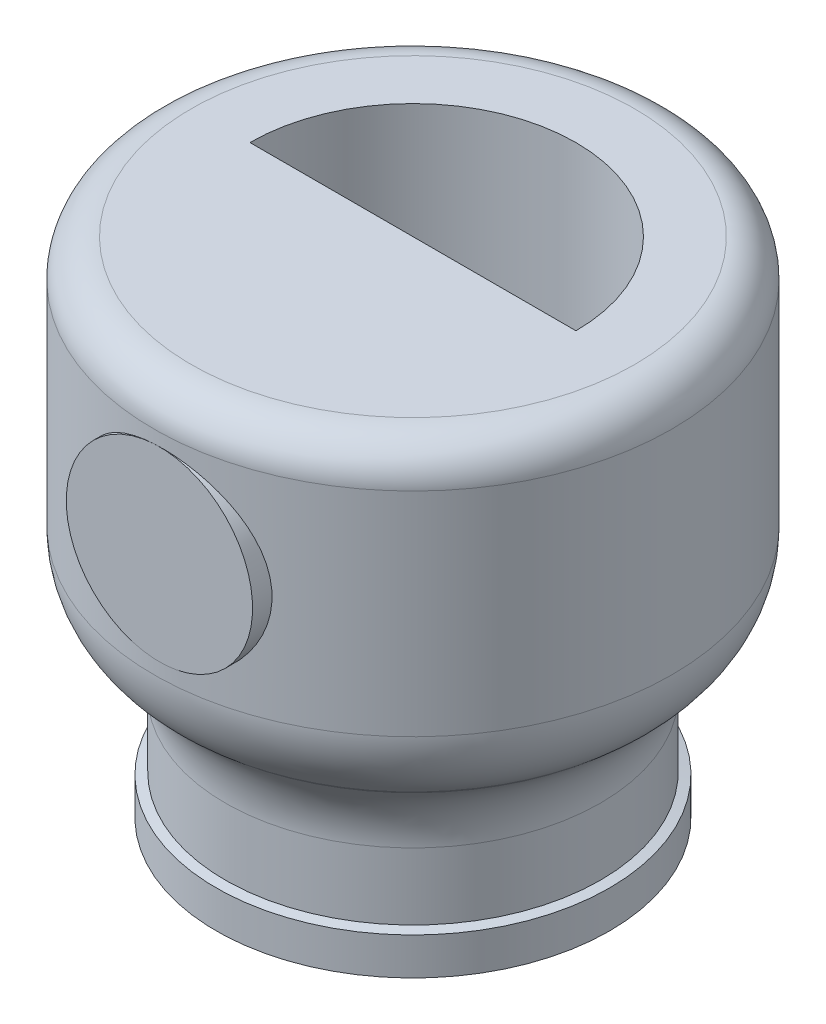
SolidWorks part; units mm, degrees
ref_plane "Front Plane" through (0, 0, 0) normal (0, 0, 1) x (1, 0, 0)
ref_plane "Top Plane" through (0, 0, 0) normal (0, 1, 0) x (1, 0, 0)
ref_plane "Right Plane" through (0, 0, 0) normal (1, 0, 0) x (0, 0, -1)
sketch "Sketch1" plane through (0, 0, 0) normal (0, 0, 1) x (1, 0, 0)
  line L0 (2.7649, 7.8218) -> (2.7649, 58.3592) construction
  line L1 (20.9, 0) -> (23.8716, 0)
  line L2 (23.8716, 0) -> (23.8716, 4)
  line L3 (23.8716, 4) -> (22.9, 4.2367)
  line L4 (22.9, 4.2367) -> (22.9, 11.4043)
  line L6 (20.9, 0) -> (20.9, 14)
  line L12 (19.9, 15) -> (2.7649, 15)
  line L17 (26.4721, 19.0648) -> (26.9883, 19.4979)
  line L18 (30.5604, 27.1583) -> (30.5604, 50)
  line L20 (26.5604, 54) -> (2.7649, 54)
  line L22 (2.7649, 15) -> (2.7649, 54)
  arc A1 (30.5604, 50) -> (26.5604, 54) centre (26.5604, 50) ccw
  arc A2 (26.4721, 19.0648) -> (22.9, 11.4043) centre (32.9, 11.4043) ccw
  arc A3 (26.9883, 19.4979) -> (30.5604, 27.1583) centre (20.5604, 27.1583) ccw
  arc A6 (20.9, 14) -> (19.9, 15) centre (19.9, 14) ccw
  point P11 (22.9, 54)
  point P28 (28.5604, 23.4279)
  point P31 (20.9, 17)
  dimension "D9" = 4
  dimension "D16" = 10
  dimension "D19" = 1
  dimension "D2" = 4
  dimension "D3" = 1
  dimension "D6" = 2
  dimension "D7" = 2.9716
  dimension "D11" = 15
  dimension "D15" = 10
revolve "Revolve1" add sketch "Sketch1" angle 360 about L0
ref_plane "Plane1" through (0, 4, 0) normal (0, 1, 0) x (1, 0, 0)
sketch "Sketch3" plane through (0, 0, 0) normal (0, 0, 1) x (1, 0, 0)
  point P0 (1.2404, 19.1989)
ref_point "Point1"
ref_plane "Plane2" through (0, 0, 22.9) normal (0, 0, 1) x (1, 0, 0)
ref_plane "Plane3" through (0, 0, 27.7955) normal (0, 0, 1) x (1, 0, 0)
ref_plane "Plane4" through (0, 54, 0) normal (0, 1, 0) x (1, 0, 0)
sketch "Sketch9" plane through (0, 54, 0) normal (0, 1, 0) x (1, 0, 0)
  line L0 (-22.2351, 0) -> (27.7649, 0)
  arc A0 (27.7649, 0) -> (-22.2351, 0) centre (2.7649, 0) ccw
  circle A3 centre (2.7649, 0) radius 23.7955 construction
  point P1 (0, 0)
  dimension "D1" = 50
  dimension "D3" = 25
  dimension "D4" = 0
sketch "Sketch10" plane through (0, 0, 27.7955) normal (0, 0, 1) x (1, 0, 0)
  line L0 (30.5604, 27.1583) -> (-25.0306, 27.1583) construction
  circle A0 centre (3.3463, 38.6583) radius 10
  dimension "D1" = 20
  dimension "D2" = 11.5
extrude "Boss-Extrude1" add sketch "Sketch10" against normal blind 5
ref_plane "Plane5" through (0, 17, 0) normal (0, 1, 0) x (1, 0, 0)
sketch "Sketch11" plane through (0, 17, 0) normal (0, 1, 0) x (1, 0, 0)
  line L0 (-14.7351, 0) -> (20.2649, 0)
  arc A1 (-14.7351, 0) -> (20.2649, 0) centre (2.7649, 0) cw
  circle A2 centre (2.7649, 0) radius 20.9233 construction
  point P6 (0, 0)
  point P7 (0, 0)
  point P8 (0, 0)
  point P9 (0, 0)
  point P10 (0, 0)
  dimension "D2" = 0
  dimension "D1" = 35
extrude "Cut-Extrude3" cut sketch "Sketch11" against normal blind 20 and the other way blind 45
